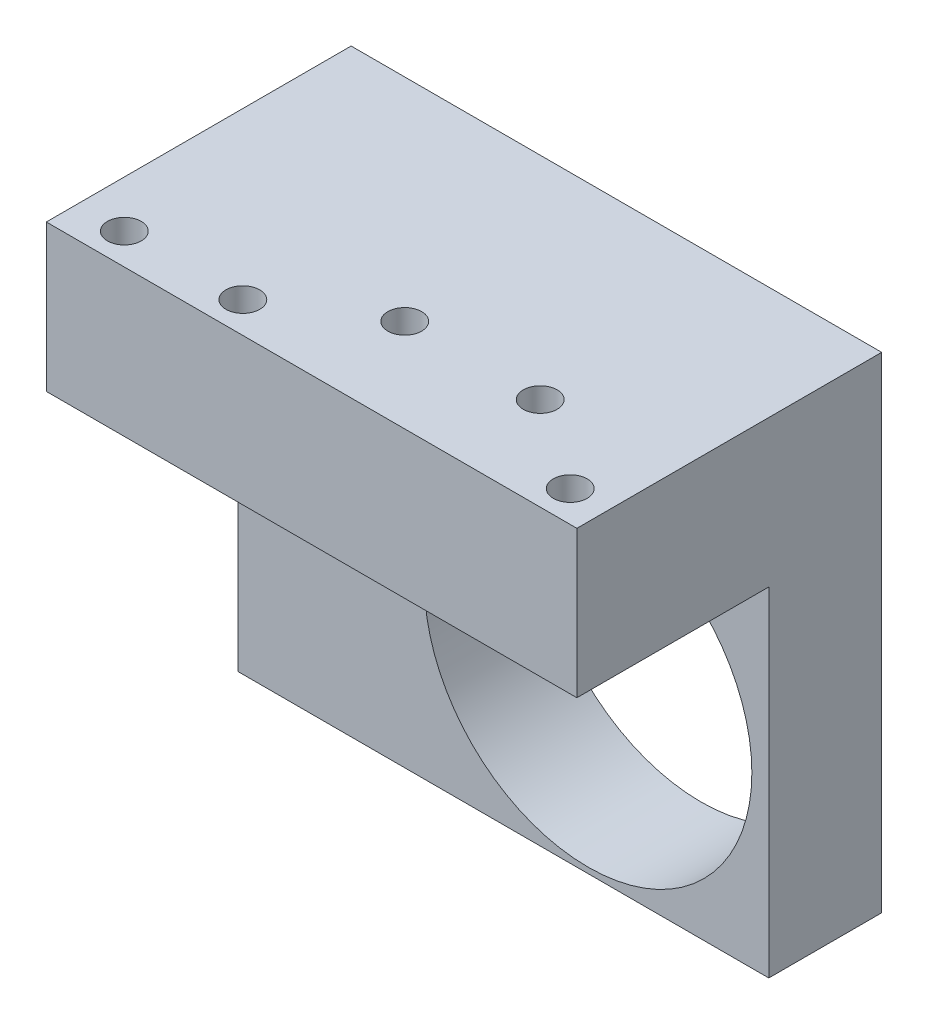
SolidWorks part; units mm, degrees
ref_plane "前视基准面" through (0, 0, 0) normal (0, 0, 1) x (1, 0, 0)
ref_plane "上视基准面" through (0, 0, 0) normal (0, 1, 0) x (1, 0, 0)
ref_plane "右视基准面" through (0, 0, 0) normal (1, 0, 0) x (0, 0, -1)
other "Configuration Table"
sketch "草图1" plane through (0, 0, 0) normal (0, 1, 0) x (1, 0, 0)
  line L0 (-23.5, 5.5) -> (-23.5, 21.5)
  line L2 (-23.5, 5.5) -> (-23.5, -5.5)
  line L3 (-23.5, -5.5) -> (23.5, -5.5)
  line L4 (23.5, 5.5) -> (23.5, -5.5)
  line L5 (-23.5, 5.5) -> (23.5, -5.5) construction
  line L6 (-23.5, -5.5) -> (23.5, 5.5) construction
  line L7 (-23.5, 21.5) -> (23.5, 21.5)
  line L8 (23.5, 21.5) -> (23.5, 5.5)
  circle A0 centre (-19.3408, -2.75) radius 1.5
  circle A1 centre (-8.8408, -2.75) radius 1.5
  circle A2 centre (20.1592, -2.75) radius 1.5
  circle A6 centre (0, 2.75) radius 1.5
  circle A7 centre (12, 2.75) radius 1.5
  point P0 (0, 0)
  dimension "D3" = 3
  dimension "D4" = 16
  dimension "D5" = 3
  dimension "D1" = 11
  dimension "D2" = 47
  dimension "D6" = 12
extrude "凸台-拉伸1" add sketch "草图1" along normal blind 13
sketch "草图3" plane through (0, 0, -21.5) normal (0, 0, -1) x (-1, 0, 0)
  line L0 (-23.5, 0) -> (-23.5, -30)
  line L1 (-23.5, -30) -> (23.5, -30)
  line L2 (23.5, -30) -> (23.5, 0)
  line L3 (23.5, 0) -> (-23.5, 0)
  circle A0 centre (-7.5, -15) radius 14.5
  dimension "D1" = 29
extrude "凸台-拉伸2" add sketch "草图3" against normal blind 10
